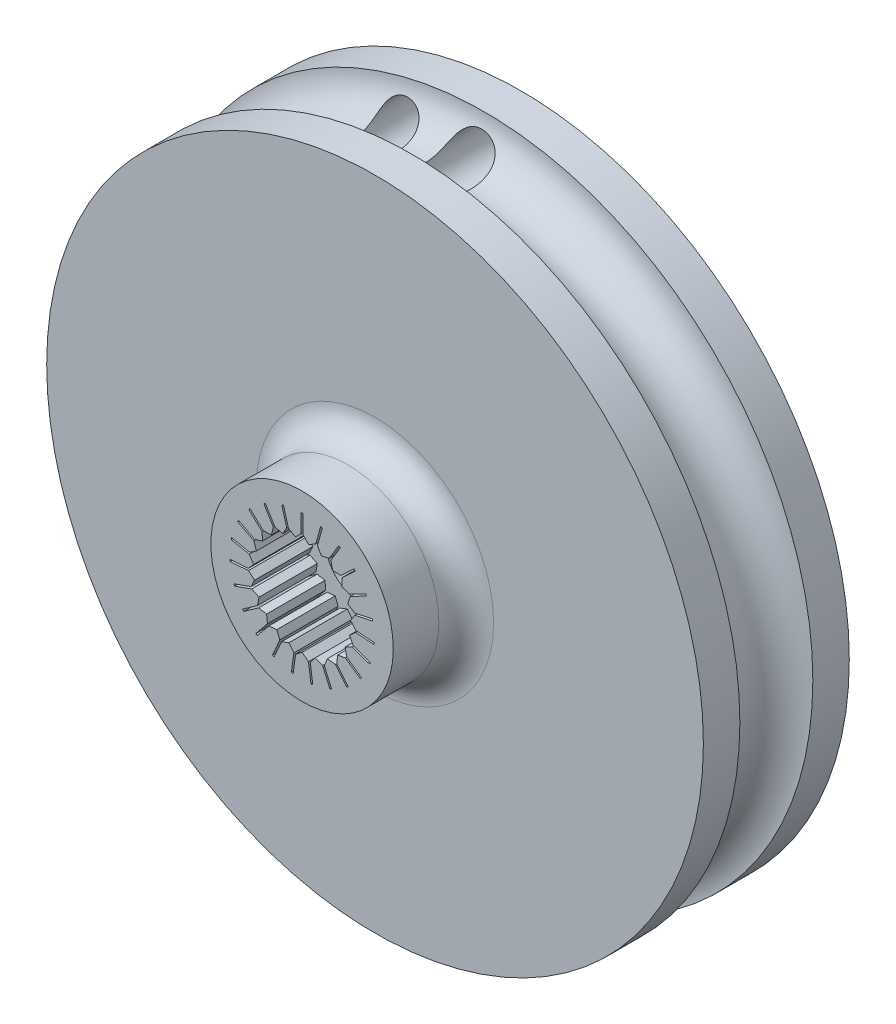
SolidWorks part; units mm, degrees
ref_plane "正面" through (0, 0, 0) normal (0, 0, 1) x (1, 0, 0)
ref_plane "平面" through (0, 0, 0) normal (0, 1, 0) x (1, 0, 0)
ref_plane "右側面" through (0, 0, 0) normal (1, 0, 0) x (0, 0, -1)
sketch "ｽｹｯﾁ8" plane through (0, 0, 0) normal (0, 1, 0) x (1, 0, 0)
  line L0 (0, 0) -> (0, 8)
  line L1 (0, 8) -> (18, 8)
  line L2 (18, 8) -> (18, 6)
  line L3 (0, 0) -> (18, 0)
  line L4 (18, 0) -> (18, 2)
  arc A0 (18, 2) -> (18, 6) centre (18, 4) cw
  point P8 (0, 0)
  point P9 (0, 4)
  point P10 (18, 3.5)
  dimension "D4" = 2
  dimension "D1" = 18
  dimension "D3" = 8
revolve "回転1" add sketch "ｽｹｯﾁ8" angle 360 about L0
sketch "ｽｹｯﾁ6" plane through (0, 0, 0) normal (0, 0, 1) x (1, 0, 0)
  circle A0 centre (0, 0) radius 5
  dimension "D1" = 10
extrude "ﾎﾞｽ - 押し出し3" add sketch "ｽｹｯﾁ6" along normal blind 4
sketch "ｽｹｯﾁ5" plane through (0, 0, 0) normal (0, 0, 1) x (1, 0, 0)
  line L0 (-0.3625, 2.6375) -> (0, 3) construction
  line L1 (0, 3) -> (0.3625, 2.6375) construction
  line L2 (-0.3625, 2.6375) -> (0, 0) construction
  line L3 (0, 0) -> (0.3625, 2.6375) construction
  line L4 (0, 3) -> (0, 0) construction
  line L5 (-0.05, 2.95) -> (-0.05, 3.95)
  line L6 (-0.05, 3.95) -> (0.05, 3.95)
  line L7 (0.05, 3.95) -> (0.05, 2.95)
  line L8 (-0.05, 2.95) -> (0.05, 2.95) construction
  line L9 (-0.3625, 2.6375) -> (-0.05, 2.95)
  line L10 (-0.05, 2.95) -> (0.05, 2.95) construction
  line L11 (0.3625, 2.6375) -> (0.05, 2.95)
  line L12 (0.3625, 2.6375) -> (0.7478, 2.8541)
  line L13 (0.7478, 2.8541) -> (1.0176, 3.817)
  line L14 (1.1138, 3.79) -> (0.844, 2.8271)
  line L15 (1.0607, 2.4419) -> (0.844, 2.8271)
  line L16 (1.0176, 3.817) -> (1.1138, 3.79)
  line L17 (1.0607, 2.4419) -> (1.4901, 2.5465)
  line L18 (1.4901, 2.5465) -> (2.0096, 3.4009)
  line L19 (2.0951, 3.349) -> (1.5755, 2.4946)
  line L20 (1.6801, 2.0652) -> (1.5755, 2.4946)
  line L21 (2.0096, 3.4009) -> (2.0951, 3.349)
  line L22 (1.6801, 2.0652) -> (2.1218, 2.0501)
  line L23 (2.1218, 2.0501) -> (2.8527, 2.7326)
  line L24 (2.9209, 2.6595) -> (2.1901, 1.977)
  line L25 (2.175, 1.5353) -> (2.1901, 1.977)
  line L26 (2.8527, 2.7326) -> (2.9209, 2.6595)
  line L27 (2.175, 1.5353) -> (2.5963, 1.4016)
  line L28 (2.5963, 1.4016) -> (3.4841, 1.8617)
  line L29 (3.5301, 1.7729) -> (2.6423, 1.3128)
  line L30 (2.5086, 0.8915) -> (2.6423, 1.3128)
  line L31 (3.4841, 1.8617) -> (3.5301, 1.7729)
  line L32 (2.5086, 0.8915) -> (2.8781, 0.6491)
  line L33 (2.8781, 0.6491) -> (3.8572, 0.8526)
  line L34 (3.8776, 0.7547) -> (2.8985, 0.5512)
  line L35 (2.6561, 0.1817) -> (2.8985, 0.5512)
  line L36 (3.8572, 0.8526) -> (3.8776, 0.7547)
  line L37 (2.6561, 0.1817) -> (2.9465, -0.1514)
  line L38 (2.9465, -0.1514) -> (3.9442, -0.2197)
  line L39 (3.9374, -0.3194) -> (2.9397, -0.2512)
  line L40 (2.6066, -0.5417) -> (2.9397, -0.2512)
  line L41 (3.9442, -0.2197) -> (3.9374, -0.3194)
  line L42 (2.6066, -0.5417) -> (2.7964, -0.9408)
  line L43 (2.7964, -0.9408) -> (3.7387, -1.2757)
  line L44 (3.7052, -1.3699) -> (2.7629, -1.035)
  line L45 (2.3638, -1.2248) -> (2.7629, -1.035)
  line L46 (3.7387, -1.2757) -> (3.7052, -1.3699)
  line L47 (2.3638, -1.2248) -> (2.4389, -1.6604)
  line L48 (2.4389, -1.6604) -> (3.2559, -2.237)
  line L49 (3.1982, -2.3187) -> (2.3812, -1.7421)
  line L50 (1.9457, -1.8171) -> (2.3812, -1.7421)
  line L51 (3.2559, -2.237) -> (3.1982, -2.3187)
  line L52 (1.9457, -1.8171) -> (1.9005, -2.2568)
  line L53 (1.9005, -2.2568) -> (2.5316, -3.0325)
  line L54 (2.454, -3.0956) -> (1.8229, -2.3199)
  line L55 (1.3833, -2.2747) -> (1.8229, -2.3199)
  line L56 (2.5316, -3.0325) -> (2.454, -3.0956)
  line L57 (1.3833, -2.2747) -> (1.2211, -2.6859)
  line L58 (1.2211, -2.6859) -> (1.6195, -3.6031)
  line L59 (1.5278, -3.6429) -> (1.1294, -2.7257)
  line L60 (0.7183, -2.5636) -> (1.1294, -2.7257)
  line L61 (1.6195, -3.6031) -> (1.5278, -3.6429)
  line L62 (0.7183, -2.5636) -> (0.4512, -2.9157)
  line L63 (0.4512, -2.9157) -> (0.5874, -3.9064)
  line L64 (0.4883, -3.92) -> (0.3522, -2.9293)
  line L65 (0, -2.6623) -> (0.3522, -2.9293)
  line L66 (0.5874, -3.9064) -> (0.4883, -3.92)
  line L67 (0, -2.6623) -> (-0.3522, -2.9293)
  line L68 (-0.3522, -2.9293) -> (-0.4883, -3.92)
  line L69 (-0.5874, -3.9064) -> (-0.4512, -2.9157)
  line L70 (-0.7183, -2.5636) -> (-0.4512, -2.9157)
  line L71 (-0.4883, -3.92) -> (-0.5874, -3.9064)
  line L72 (-0.7183, -2.5636) -> (-1.1294, -2.7257)
  line L73 (-1.1294, -2.7257) -> (-1.5278, -3.6429)
  line L74 (-1.6195, -3.6031) -> (-1.2211, -2.6859)
  line L75 (-1.3833, -2.2747) -> (-1.2211, -2.6859)
  line L76 (-1.5278, -3.6429) -> (-1.6195, -3.6031)
  line L77 (-1.3833, -2.2747) -> (-1.8229, -2.3199)
  line L78 (-1.8229, -2.3199) -> (-2.454, -3.0956)
  line L79 (-2.5316, -3.0325) -> (-1.9005, -2.2568)
  line L80 (-1.9457, -1.8171) -> (-1.9005, -2.2568)
  line L81 (-2.454, -3.0956) -> (-2.5316, -3.0325)
  line L82 (-1.9457, -1.8171) -> (-2.3812, -1.7421)
  line L83 (-2.3812, -1.7421) -> (-3.1982, -2.3187)
  line L84 (-3.2559, -2.237) -> (-2.4389, -1.6604)
  line L85 (-2.3638, -1.2248) -> (-2.4389, -1.6604)
  line L86 (-3.1982, -2.3187) -> (-3.2559, -2.237)
  line L87 (-2.3638, -1.2248) -> (-2.7629, -1.035)
  line L88 (-2.7629, -1.035) -> (-3.7052, -1.3699)
  line L89 (-3.7387, -1.2757) -> (-2.7964, -0.9408)
  line L90 (-2.6066, -0.5417) -> (-2.7964, -0.9408)
  line L91 (-3.7052, -1.3699) -> (-3.7387, -1.2757)
  line L92 (-2.6066, -0.5417) -> (-2.9397, -0.2512)
  line L93 (-2.9397, -0.2512) -> (-3.9374, -0.3194)
  line L94 (-3.9442, -0.2197) -> (-2.9465, -0.1514)
  line L95 (-2.6561, 0.1817) -> (-2.9465, -0.1514)
  line L96 (-3.9374, -0.3194) -> (-3.9442, -0.2197)
  line L97 (-2.6561, 0.1817) -> (-2.8985, 0.5512)
  line L98 (-2.8985, 0.5512) -> (-3.8776, 0.7547)
  line L99 (-3.8572, 0.8526) -> (-2.8781, 0.6491)
  line L100 (-2.5086, 0.8915) -> (-2.8781, 0.6491)
  line L101 (-3.8776, 0.7547) -> (-3.8572, 0.8526)
  line L102 (-2.5086, 0.8915) -> (-2.6423, 1.3128)
  line L103 (-2.6423, 1.3128) -> (-3.5301, 1.7729)
  line L104 (-3.4841, 1.8617) -> (-2.5963, 1.4016)
  line L105 (-2.175, 1.5353) -> (-2.5963, 1.4016)
  line L106 (-3.5301, 1.7729) -> (-3.4841, 1.8617)
  line L107 (-2.175, 1.5353) -> (-2.1901, 1.977)
  line L108 (-2.1901, 1.977) -> (-2.9209, 2.6595)
  line L109 (-2.8527, 2.7326) -> (-2.1218, 2.0501)
  line L110 (-1.6801, 2.0652) -> (-2.1218, 2.0501)
  line L111 (-2.9209, 2.6595) -> (-2.8527, 2.7326)
  line L112 (-1.6801, 2.0652) -> (-1.5755, 2.4946)
  line L113 (-1.5755, 2.4946) -> (-2.0951, 3.349)
  line L114 (-2.0096, 3.4009) -> (-1.4901, 2.5465)
  line L115 (-1.0607, 2.4419) -> (-1.4901, 2.5465)
  line L116 (-2.0951, 3.349) -> (-2.0096, 3.4009)
  line L117 (-1.0607, 2.4419) -> (-0.844, 2.8271)
  line L118 (-0.844, 2.8271) -> (-1.1138, 3.79)
  line L119 (-1.0176, 3.817) -> (-0.7478, 2.8541)
  line L120 (-0.3625, 2.6375) -> (-0.7478, 2.8541)
  line L121 (-1.1138, 3.79) -> (-1.0176, 3.817)
  circle A0 centre (0, 0) radius 3 construction
  circle A1 centre (0, 0) radius 2.6623 construction
  point P147 (0, 0)
  dimension "D1" = 6
  dimension "D2" = 7.826
  dimension "D3" = 7.826
  dimension "D4" = 0.1
  dimension "D5" = 1
  dimension "D6" = 23
extrude "ｶｯﾄ - 押し出し5" cut sketch "ｽｹｯﾁ5" against normal blind 3.2 from surface starting at face at (5, 0, 4)
fillet "ﾌｨﾚｯﾄ2" radius 1.5 1 edges at (5, 0, 0)
sketch "ｽｹｯﾁ9" plane through (0, 0, -8) normal (0, 0, -1) x (-1, 0, 0)
  circle A0 centre (0, 0) radius 1.9
  dimension "D1" = 3.8
extrude "ｶｯﾄ - 押し出し6" cut sketch "ｽｹｯﾁ9" against normal through all
sketch "ｽｹｯﾁ10" plane through (0, 0, -8) normal (0, 0, -1) x (-1, 0, 0)
  circle A0 centre (0, 0) radius 3
  dimension "D1" = 6
extrude "ｶｯﾄ - 押し出し7" cut sketch "ｽｹｯﾁ10" against normal offset from surface (3.8 mm away) 5 up to face at (1.9, 0, 0.8)
sketch "ｽｹｯﾁ11" plane through (0, 0, -8) normal (0, 0, 1) x (1, 0, 0)
  circle A0 centre (0, 0) radius 16 construction
  circle A1 centre (0, 16) radius 1.25
  circle A2 centre (-3.9686, 15.5) radius 1.25
  dimension "D1" = 2.5
  dimension "D2" = 32
  dimension "D3" = 4
extrude "ｶｯﾄ - 押し出し8" cut sketch "ｽｹｯﾁ11" along normal blind 5 contours A1 | A2
equation "\"18.4.300mm\"= 18.3"
equation "\"D2@ｽｹｯﾁ5\"=360deg/46"
equation "\"D3@ｽｹｯﾁ5\"=\"D2@ｽｹｯﾁ5\""
